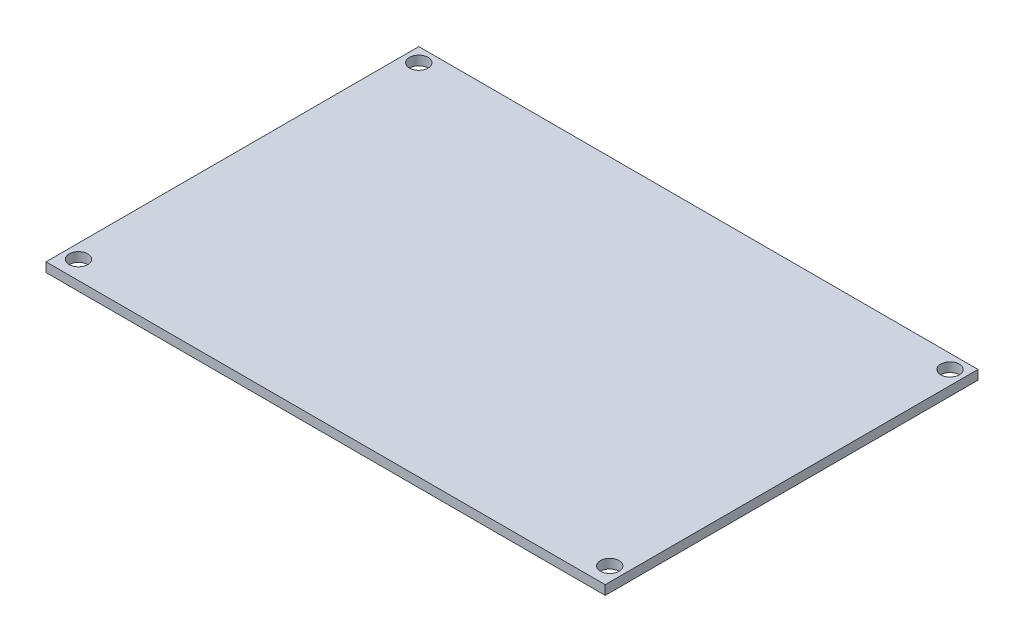
SolidWorks part; units mm, degrees
ref_plane "Front Plane" through (0, 0, 0) normal (0, 0, 1) x (1, 0, 0)
ref_plane "Top Plane" through (0, 0, 0) normal (0, 1, 0) x (1, 0, 0)
ref_plane "Right Plane" through (0, 0, 0) normal (1, 0, 0) x (0, 0, -1)
sketch "Sketch1" plane through (0, 0, 0) normal (0, 1, 0) x (1, 0, 0)
  line L1 (-60, -40) -> (60, -40)
  line L2 (-60, -40) -> (-60, 40)
  line L3 (-60, 40) -> (60, 40)
  line L4 (60, -40) -> (60, 40)
  line L5 (-60, -40) -> (60, 40) construction
  line L6 (-60, 40) -> (60, -40) construction
  point P0 (0, 0)
  dimension "D1" = 120
  dimension "D2" = 80
extrude "Boss-Extrude1" add sketch "Sketch1" along normal blind 2
sketch "Sketch2" plane through (0, 2, 0) normal (0, 1, 0) x (1, 0, 0)
  circle A0 centre (-57, 37) radius 2
  circle A1 centre (57, 37) radius 2
  circle A2 centre (57, -36.0288) radius 2
  circle A3 centre (-57, -36.0288) radius 2
  point P0 (0, 0)
  dimension "D3" = 4
extrude "Cut-Extrude1" cut sketch "Sketch2" against normal blind 10 and the other way blind 10
